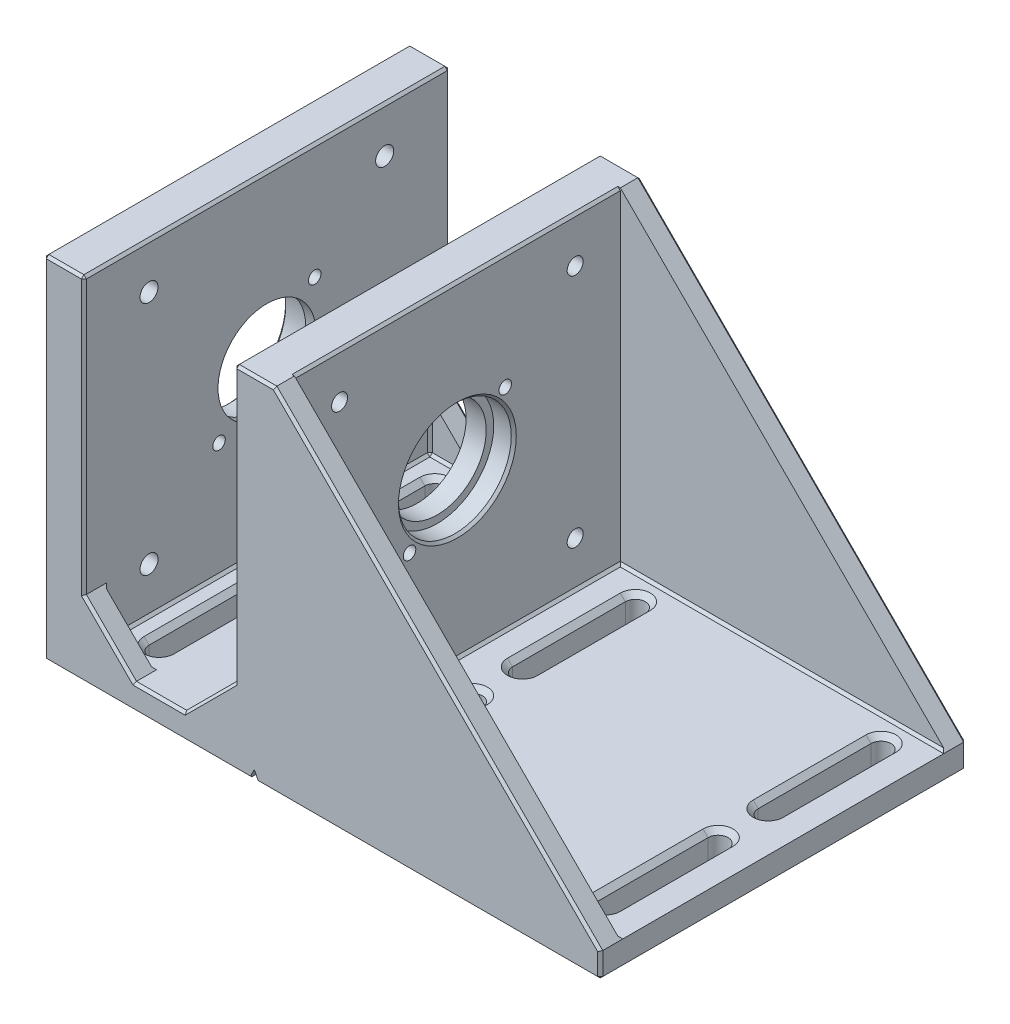
SolidWorks part; units mm, degrees
ref_plane "Front Plane" through (0, 0, 0) normal (0, 0, 1) x (1, 0, 0)
ref_plane "Top Plane" through (0, 0, 0) normal (0, 1, 0) x (1, 0, 0)
ref_plane "Right Plane" through (0, 0, 0) normal (1, 0, 0) x (0, 0, -1)
sketch "Sketch1" plane through (0, 0, 0) normal (0, 0, 1) x (1, 0, 0)
  line L0 (-8, 32.5) -> (-8, -22.5)
  line L1 (-18, -32.5) -> (-28, -32.5)
  line L2 (-38, -22.5) -> (-38, 32.5)
  line L3 (-38, 32.5) -> (-46, 32.5)
  line L4 (-46, 32.5) -> (-46, -37.5)
  line L5 (-46, -37.5) -> (65, -37.5)
  line L6 (65, -37.5) -> (65, -32.5)
  line L8 (65, -32.5) -> (0, 32.5)
  line L9 (0, 32.5) -> (-8, 32.5)
  line L10 (-28, -32.5) -> (-38, -22.5)
  line L11 (-8, -22.5) -> (-18, -32.5)
  point P1 (-8, -32.5)
  point P3 (-38, -32.5)
  dimension "D1" = 65
  dimension "D2" = 30
  dimension "D3" = 5
  dimension "D4" = 8
  dimension "D5" = 8
  dimension "D6" = 45
  dimension "D7" = 32.5
extrude "Boss-Extrude1" add sketch "Sketch1" along normal mid plane 73
sketch "Sketch2" plane through (0, 0, 0) normal (0, 0, 1) x (1, 0, 0)
  line L0 (-38, 32.5) -> (-38, -32.5)
  line L1 (-38, -32.5) -> (-8, -32.5)
  line L2 (-8, -32.5) -> (-8, 32.5)
  line L3 (-18, -32.5) -> (-28, -32.5) construction
  line L4 (-8, 32.5) -> (-38, 32.5)
  line L5 (0, 32.5) -> (0, -32.5)
  line L6 (0, -32.5) -> (65, -32.5)
  line L7 (65, -32.5) -> (0, 32.5)
extrude "Cut-Extrude1" cut sketch "Sketch2" along normal offset from surface 4 and the other way offset from surface 4 up to face at (-9.0909, -7.9545, 36.5) other way up to face at (-9.0909, -7.9545, -36.5)
sketch "Sketch3" plane through (0, 0, 0) normal (1, 0, 0) x (0, 0, -1)
  circle A0 centre (0, 0) radius 11.25
  dimension "D1" = 22.5
extrude "Cut-Extrude2" cut sketch "Sketch3" against normal through all both and the other way through all
sketch "Sketch4" plane through (-38, 0, 0) normal (-1, 0, 0) x (0, 0, 1)
  circle A1 centre (0, 0) radius 11.25 construction
  circle A2 centre (0, 0) radius 9.75
  circle A3 centre (0, 0) radius 9.75
  circle A4 centre (0, 0) radius 11.25
  dimension "D1" = 1.5
extrude "Boss-Extrude2" add sketch "Sketch4" along normal blind 2
hole_wizard "Tap Drill for M3x0.5 Tap1" positions "Sketch8" profile "Sketch10" hole size "M3x0.5" standard "ANSI Metric" end condition through all
sketch "Sketch8" plane through (-46, 0, 0) normal (-1, 0, 0) x (0, 0, 1)
  line L0 (-9.5459, 9.5459) -> (9.5459, -9.5459)
  line L2 (36.5, 32.5) -> (-36.5, 32.5) construction
  point P0 (-9.5459, 9.5459)
  point P2 (9.5459, -9.5459)
  point P11 (0, 0)
  dimension "D1" = 45
  dimension "D2" = 27
sketch "Sketch10" plane through (-46, 9.5459, -9.5459) normal (0, 1, 0) x (0, 0, 1)
  line L0 (0, 0) -> (0, 111)
  line L1 (0, 111) -> (1.25, 111)
  line L2 (1.25, 111) -> (1.25, 0)
  line L5 (1.25, 0) -> (0, 0)
  line L11 (0, -6.35) -> (0, 107.95) construction
  dimension "Thru Hole Dia." = 2.5
  dimension "Thru Hole Depth" = 111
hole_wizard "CSK for M3 Flat Head Machine Screw1" positions "Sketch12" profile "Sketch13" countersink size "M3" standard "ANSI Metric" end condition up to next
sketch "Sketch12" plane through (-8, 0, 0) normal (-1, 0, 0) x (0, 0, 1)
  line L1 (23.5, -23.5) -> (-23.5, -23.5) construction
  line L2 (23.5, -23.5) -> (23.5, 23.5) construction
  line L3 (23.5, 23.5) -> (-23.5, 23.5) construction
  line L4 (-23.5, -23.5) -> (-23.5, 23.5) construction
  line L5 (23.5, -23.5) -> (-23.5, 23.5) construction
  line L6 (23.5, 23.5) -> (-23.5, -23.5) construction
  point P0 (-23.5, 23.5)
  point P2 (23.5, 23.5)
  point P4 (23.5, -23.5)
  point P6 (-23.5, -23.5)
  point P9 (0, 0)
  dimension "D1" = 47
sketch "Sketch13" plane through (-8, 23.5, -23.5) normal (0, 1, 0) x (0, 0, 1)
  line L0 (0, 0) -> (0, 8)
  line L1 (0, 8) -> (1.6, 8)
  line L2 (1.6, 8) -> (1.6, 1.55)
  line L3 (1.6, 1.55) -> (3.15, 0)
  line L5 (3.15, 0) -> (0, 0)
  line L6 (-1.6, 1.55) -> (-3.15, 0) construction
  line L11 (0, -6.35) -> (0, 107.95) construction
  dimension "Thru Hole Dia." = 3.2
  dimension "Thru Hole Depth" = 8
  dimension "Near C'Sink Dia." = 6.3
  dimension "Near C'Sink Angle" = 90
sketch "Sketch21" plane through (0, 0, 0) normal (0, 0, 1) x (1, 0, 0)
  line L0 (-5, -37.5) -> (-4, -35.5)
  line L1 (-46, -37.5) -> (65, -37.5) construction
  line L2 (-4, -35.5) -> (-3, -37.5)
  line L3 (-3, -37.5) -> (-5, -37.5)
  line L4 (0, 32.5) -> (-8, 32.5) construction
  point P8 (-4, 32.5)
  dimension "D1" = 2
  dimension "D2" = 2
extrude "Cut-Extrude4" cut sketch "Sketch21" against normal through all both and the other way through all
chamfer "Chamfer1" distance 0.5 angle 45 45 edges at (0, 11.25, 0) (-46, 0, -11.25) (-8, -27.5, -32.5) (-8, -27.5, 32.5) (-13, -32.5, 32.5) (-8, -32.5, 0) (-13, -32.5, -32.5) (-38, -27.5, 32.5) (-38, -27.5, -32.5) (-33, -32.5, -32.5) (-38, -32.5, 0) (-33, -32.5, 32.5) (32.5, -32.5, 32.5) (0, -32.5, 0) (32.5, -32.5, -32.5) (0, 32.5, 0) (-8, 32.5, 0) (-4, 32.5, 36.5) (-8, 5, 36.5) (-13, -27.5, 36.5) (-23, -32.5, 36.5) (-33, -27.5, 36.5) (-38, 5, 36.5) (-42, 32.5, 36.5) (-38, 32.5, 0) (-46, 32.5, 0) (-42, 32.5, -36.5) (-38, 5, -36.5) (-33, -27.5, -36.5) (-23, -32.5, -36.5) (-13, -27.5, -36.5) (-8, 5, -36.5) (-4, 32.5, -36.5) (32.5, 0, 36.5) (32.5, 0, -36.5) (65, -35, 36.5) (65, -35, -36.5) (-46, -2.5, -36.5) (-46, -2.5, 36.5) (65, -37.5, 0) (-25.5, -37.5, -36.5) (31, -37.5, -36.5) (-46, -37.5, 0) (31, -37.5, 36.5) (-25.5, -37.5, 36.5)
extrude "Boss-Extrude3" add sketch "Sketch4<2>" against normal blind 4 from surface starting at face at (-8, -11.25, 0)
sketch "Sketch4<2>" plane through (-38, 0, 0) normal (-1, 0, 0) x (0, 0, 1) same geometry as "Sketch4"
hole_wizard "M3 Clearance Hole1" positions "Sketch18" profile "Sketch17" hole size "M3" standard "ANSI Metric" end condition up to next
sketch "Sketch18" plane through (-46, 0, 0) normal (-1, 0, 0) x (0, 0, 1)
  circle A0 centre (-23.5, -23.5) radius 1.6 construction
  circle A1 centre (23.5, -23.5) radius 1.6 construction
  circle A2 centre (23.5, 23.5) radius 1.6 construction
  circle A3 centre (-23.5, 23.5) radius 1.6 construction
  circle A4 centre (-23.5, -23.5) radius 1.6
  circle A5 centre (23.5, -23.5) radius 1.6
  circle A6 centre (23.5, 23.5) radius 1.6
  circle A7 centre (-23.5, 23.5) radius 1.6
  point P1 (-23.5, -23.5)
  point P3 (23.5, -23.5)
  point P5 (23.5, 23.5)
  point P7 (-23.5, 23.5)
sketch "Sketch17" plane through (-46, -23.5, -23.5) normal (0, 1, 0) x (0, 0, 1)
  line L0 (0, 0) -> (0, 8)
  line L1 (0, 8) -> (1.8, 8)
  line L2 (1.8, 8) -> (1.8, 0)
  line L5 (1.8, 0) -> (0, 0)
  line L11 (0, -6.35) -> (0, 107.95) construction
  dimension "Thru Hole Dia." = 3.6
  dimension "Thru Hole Depth" = 8
sketch "Sketch19" plane through (0, -32.5, 0) normal (0, 1, 0) x (1, 0, 0)
  line L0 (-32, 5) -> (-32, 27.5) construction
  line L1 (-34, 5) -> (-34, 27.5)
  line L2 (-30, 5) -> (-30, 27.5)
  line L3 (-14, 5) -> (-14, 27.5) construction
  line L4 (-16, 5) -> (-16, 27.5)
  line L5 (-12, 5) -> (-12, 27.5)
  line L6 (-17.5, 32.5) -> (-8.5, 32.5) construction
  line L7 (-38, -32) -> (-38, 32) construction
  line L8 (-8, -36) -> (-8, 36) construction
  line L9 (8, 5) -> (8, 27.5) construction
  line L10 (6, 5) -> (6, 27.5)
  line L11 (10, 5) -> (10, 27.5)
  line L12 (57, 5) -> (57, 27.5) construction
  line L13 (55, 5) -> (55, 27.5)
  line L14 (59, 5) -> (59, 27.5)
  line L16 (0, -32.5) -> (0, 32.5) construction
  line L17 (65, -32) -> (65, 32) construction
  arc A0 (-34, 5) -> (-30, 5) centre (-32, 5) ccw
  arc A1 (-30, 27.5) -> (-34, 27.5) centre (-32, 27.5) ccw
  arc A2 (-16, 5) -> (-12, 5) centre (-14, 5) ccw
  arc A3 (-12, 27.5) -> (-16, 27.5) centre (-14, 27.5) ccw
  arc A4 (6, 5) -> (10, 5) centre (8, 5) ccw
  arc A5 (10, 27.5) -> (6, 27.5) centre (8, 27.5) ccw
  arc A6 (55, 5) -> (59, 5) centre (57, 5) ccw
  arc A7 (59, 27.5) -> (55, 27.5) centre (57, 27.5) ccw
  point P2 (-32, 16.25)
  point P7 (-14, 16.25)
  point P21 (8, 16.25)
  point P28 (57, 16.25)
  dimension "D3" = 2
  dimension "D1" = 5
  dimension "D2" = 5
  dimension "D4" = 6
  dimension "D5" = 6
  dimension "D6" = 8
  dimension "D7" = 8
extrude "Cut-Extrude3" cut sketch "Sketch19" against normal through all
chamfer "Chamfer2" distance 1 angle 45 16 edges at (59, -32.5, -16.25) (57, -32.5, -29.5) (57, -32.5, -3) (55, -32.5, -16.25) (10, -32.5, -16.25) (8, -32.5, -29.5) (8, -32.5, -3) (6, -32.5, -16.25) (-12, -32.5, -16.25) (-14, -32.5, -29.5) (-14, -32.5, -3) (-16, -32.5, -16.25) (-34, -32.5, -16.25) (-32, -32.5, -3) (-32, -32.5, -29.5) (-30, -32.5, -16.25)
mirror "Mirror1" about plane through (0, 0, 0) normal (0, 0, 1) of "Chamfer2", "Cut-Extrude3"
